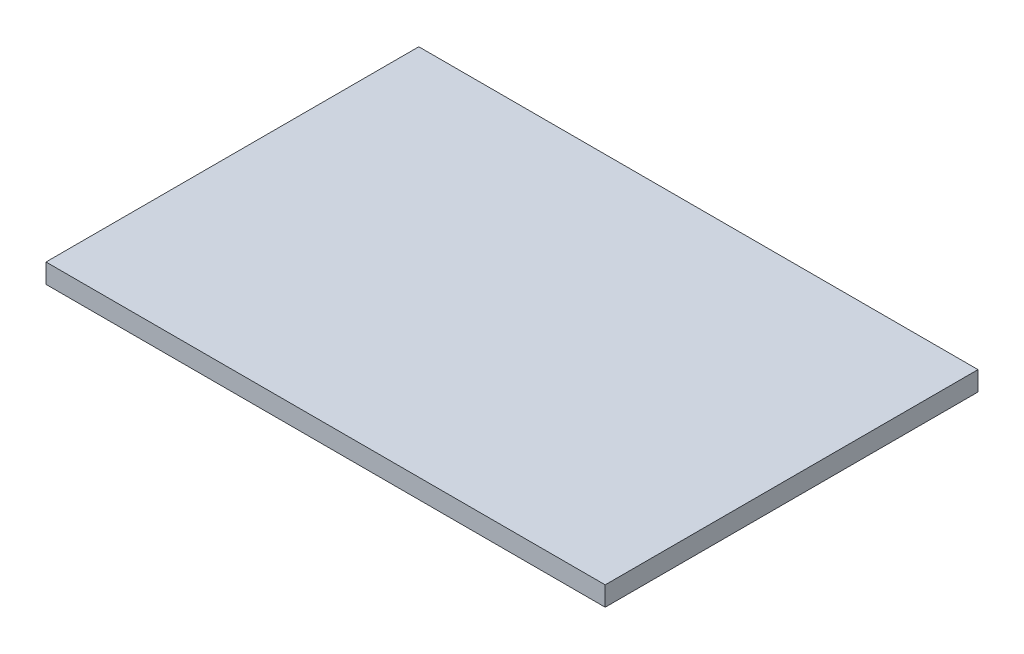
SolidWorks part; units mm, degrees
material "Cedar"
ref_plane "Front Plane" through (0, 0, 0) normal (0, 0, 1) x (1, 0, 0)
ref_plane "Top Plane" through (0, 0, 0) normal (0, 1, 0) x (1, 0, 0)
ref_plane "Right Plane" through (0, 0, 0) normal (1, 0, 0) x (0, 0, -1)
sketch "Sketch1" plane through (0, 0, 0) normal (0, 1, 0) x (1, 0, 0)
  line L1 (-457.2, -304.8) -> (457.2, -304.8)
  line L2 (-457.2, -304.8) -> (-457.2, 304.8)
  line L3 (-457.2, 304.8) -> (457.2, 304.8)
  line L4 (457.2, -304.8) -> (457.2, 304.8)
  line L5 (-457.2, -304.8) -> (457.2, 304.8) construction
  line L6 (-457.2, 304.8) -> (457.2, -304.8) construction
  point P0 (0, 0)
  dimension "D1" = 914.4
  dimension "D2" = 609.6
extrude "Boss-Extrude1" add sketch "Sketch1" along normal blind 31.75
